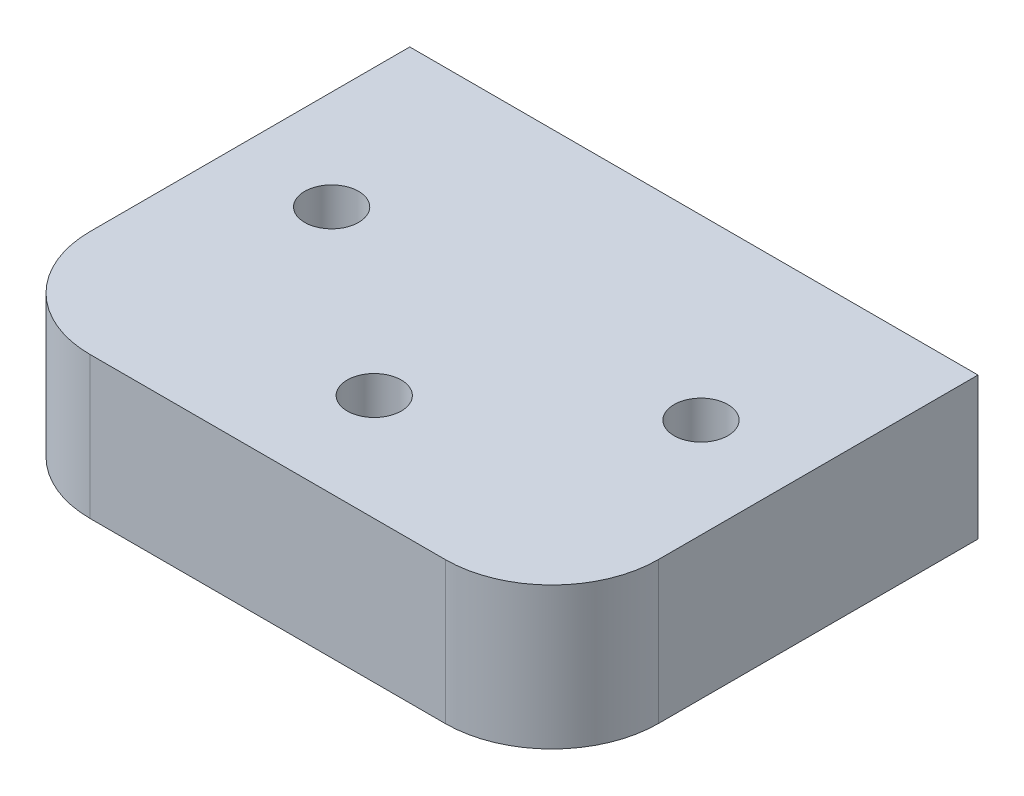
SolidWorks part; units mm, degrees
ref_plane "Front Plane" through (0, 0, 0) normal (0, 0, 1) x (1, 0, 0)
ref_plane "Top Plane" through (0, 0, 0) normal (0, 1, 0) x (1, 0, 0)
ref_plane "Right Plane" through (0, 0, 0) normal (1, 0, 0) x (0, 0, -1)
sketch "Sketch1" plane through (0, 0, 0) normal (0, 1, 0) x (1, 0, 0)
  line L1 (0, 0) -> (40, 0)
  line L2 (0, 0) -> (0, -22.5)
  line L3 (7.5, -30) -> (32.5, -30)
  line L4 (40, 0) -> (40, -22.5)
  arc A0 (32.5, -30) -> (40, -22.5) centre (32.5, -22.5) ccw
  arc A1 (0, -22.5) -> (7.5, -30) centre (7.5, -22.5) ccw
  point P9 (0, -30)
  dimension "D3" = 7.5
  dimension "D1" = 40
  dimension "D2" = 30
extrude "Boss-Extrude1" add sketch "Sketch1" along normal blind 10
hole_wizard "#6 Clearance Hole1" positions "Sketch2" profile "Sketch3" hole size "#6" standard "ANSI Inch" end condition through all
sketch "Sketch2" plane through (0, 10, 0) normal (0, 1, 0) x (1, 0, 0)
  line L0 (7.5, -30) -> (32.5, -30) construction
  point P0 (7, -12.5)
  point P2 (33, -12.5)
  point P4 (20, -22.5)
  point P10 (20, -30)
  dimension "D1" = 10
  dimension "D2" = 26
  dimension "D3" = 13
sketch "Sketch3" plane through (7, 10, 12.5) normal (1, 0, 0) x (0, 0, 1)
  line L0 (0, 0) -> (0, 10)
  line L1 (0, 10) -> (1.8986, 10)
  line L2 (1.8986, 10) -> (1.8986, 0)
  line L5 (1.8986, 0) -> (0, 0)
  line L11 (0, -6.35) -> (0, 107.95) construction
  dimension "Thru Hole Dia." = 3.7973
  dimension "Thru Hole Depth" = 10
hole_wizard "#4-40 Tapped Hole1" positions "Sketch4" profile "Sketch6" tap size "#4-40" standard "ANSI Inch"
sketch "Sketch4" plane through (0, 0, 0) normal (0, 0, -1) x (-1, 0, 0)
  line L1 (-40, 10) -> (-40, 0) construction
  line L2 (-40, 0) -> (0, 0) construction
  point P0 (-32.5, 5)
  point P2 (-20, 5)
  point P4 (-7.5, 5)
  point P12 (-40, 5)
  point P16 (-20, 0)
  dimension "D1" = 12.5
  dimension "D2" = 12.5
sketch "Sketch6" plane through (32.5, 5, 0) normal (1, 0, 0) x (0, 1, 0)
  line L0 (0, 0) -> (0, 8.2792)
  line L1 (0, 8.2792) -> (1.1303, 7.6)
  line L2 (1.1303, 7.6) -> (1.1303, 0)
  line L5 (1.1303, 0) -> (0, 0)
  line L10 (0, 8.2792) -> (-1.1303, 7.6) construction
  line L11 (0, -6.35) -> (0, 107.95) construction
  dimension "Tap Drill Dia." = 2.2606
  dimension "Tap Drill Depth" = 7.6
  dimension "Drill Angle" = 118
